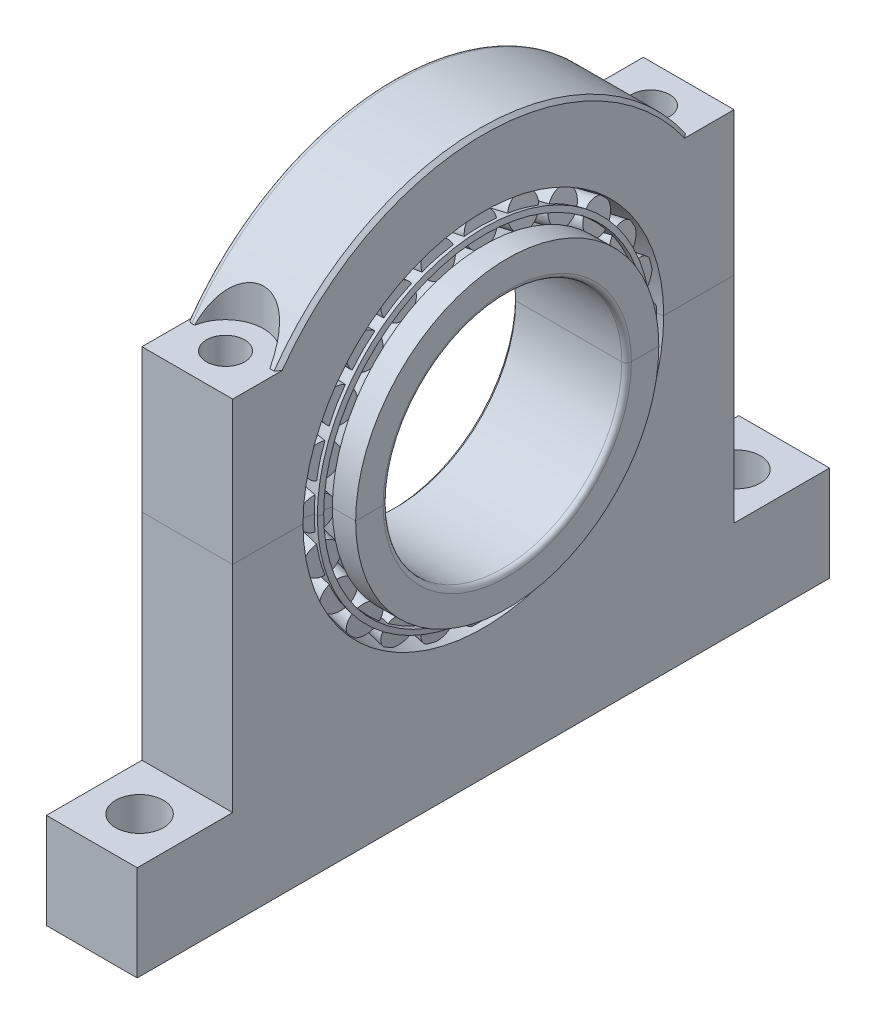
SolidWorks part; units mm, degrees
revolve "OuterRace" add sketch "OutRacSke" angle 360 about L5
sketch "OutRacSke" plane through (0, 0, 0) normal (0, 0, 1) x (1, 0, 0)
  line L0 (-5, 37.7704) -> (-24, 33.8875)
  line L1 (-24, 33.8875) -> (-24, 51.5)
  line L2 (-23, 52.5) -> (-5.76, 52.5)
  line L3 (-5.76, 52.5) -> (-5, 51.74)
  line L4 (-5, 51.74) -> (-5, 37.7704)
  line L5 (-42.5, 0) -> (42.5, 0) construction
  arc A0 (-24, 51.5) -> (-23, 52.5) centre (-23, 51.5) cw
  dimension "D8" = 45
  dimension "Tangle" = 11.55
ref_plane "Plane1" through (0, 0, 0) normal (0, 0, 1) x (1, 0, 0)
ref_plane "Plane2" through (0, 0, 0) normal (0, 1, 0) x (1, 0, 0)
ref_plane "Plane3" through (0, 0, 0) normal (1, 0, 0) x (0, 0, -1)
sketch "Clipboard" plane through (0, 0, 0) normal (0, 0, 1) x (1, 0, 0)
  line L0 (0, 0) -> (10, 0) construction
  line L1 (0, 0) -> (61.9155, -27.5666)
  line L2 (0, 0) -> (45.6773, 20.3368)
  line L3 (0, 0) -> (73.0836, -32.5389)
  line L4 (0, 0) -> (-17.0896, -0.5968)
  line L5 (0, 0) -> (-6.75, 24)
  dimension "Roller_diameter" = 6.75
  dimension "cyl_len" = 17.1
sketch "RolDetSke" plane through (0, 0, 0) normal (0, 0, 1) x (1, 0, 0)
  line L0 (-22.3242, 30.9557) -> (-23, 34.2623)
  line L1 (-22.3242, 30.9557) -> (-5.5705, 34.3795)
  line L2 (-6.2463, 37.6861) -> (-5.5705, 34.3795)
  line L4 (-44.7614, 26.3704) -> (4.5907, 36.456) construction
  line L5 (-6.2463, 37.6861) -> (-23, 34.2623)
  line L9 (-5, 37.7704) -> (-24, 33.8875) construction
  dimension "Roller_diameter" = 6.75
  dimension "dy" = 34.2623
  dimension "D2" = 23
  dimension "cyl_len" = 17.1
revolve "RollerDetailed" add sketch "RolDetSke" angle 360 about L4
sketch "RolSimSke" plane through (0, 0, 0) normal (0, 0, 1) x (1, 0, 0)
  line L0 (0, 0) -> (-32, 0) construction
  line L1 (-23, 34.2623) -> (-6.2463, 37.6861)
  line L2 (-23, 34.2623) -> (-21.6485, 27.649)
  line L3 (-21.6485, 27.649) -> (-4.8948, 31.0728)
  line L4 (-6.2463, 37.6861) -> (-4.8948, 31.0728)
  dimension "Roller_diameter" = 6.75
  dimension "dy" = 34.2623
  dimension "dx" = 23
  dimension "Tangle" = 11.55
revolve "RollersSimplified" [suppressed] add sketch "RolSimSke" angle 360 about L0
ref_axis "Axis1" through (-50, 0, 0) along (1, 0, 0)
pattern_circular "RollersDetailed" count 24 every 15 about axis through (-50, 0, 0) along (1, 0, 0) of "RollerDetailed", "OuterRace"
sketch "InsRacSke" plane through (0, 0, 0) normal (0, 0, 1) x (1, 0, 0)
  line L0 (-21.7107, 27.9865) -> (-24, 27.9865)
  line L1 (-24, 51.5) -> (-24, -51.5) construction
  line L2 (-24, 27.9865) -> (-24, 25.76)
  line L3 (-24, 25.76) -> (-23.24, 25)
  line L4 (-23.24, 25) -> (-1, 25)
  line L5 (0, 26) -> (0, 31.7478)
  line L6 (0, 31.7478) -> (-4.888, 31.7478)
  line L7 (-4.888, 31.7478) -> (-4.888, 31.0728)
  line L8 (-4.888, 31.0728) -> (-21.6417, 27.649)
  line L9 (-21.6417, 27.649) -> (-21.7107, 27.9865)
  line L10 (-42.5, 0) -> (42.5, 0) construction
  arc A0 (-1, 25) -> (0, 26) centre (-1, 26) ccw
  dimension "Tangle" = 11.55
  dimension "cyl_len" = 17.1
  dimension "dy" = 27.649
  dimension "dx" = 21.6417
  dimension "D11" = 45
  dimension "D2" = 24
revolve "InnerRace" add sketch "InsRacSke" angle 360 about L10
sketch "CagSpiSke" plane through (0, 0, 0) normal (0, 0, 1) x (1, 0, 0)
  line L3 (-4.7328, 34.3802) -> (-22.3242, 30.7852)
  line L4 (-22.675, 30.2542) -> (-22.4948, 29.3724)
  line L6 (-42.5, 0) -> (42.5, 0) construction
  arc A1 (-22.3242, 30.7852) -> (-22.675, 30.2542) centre (-22.2341, 30.3443) ccw
  dimension "Tangle" = 11.55
  dimension "radius" = 0.45
  dimension "dx" = 22.3242
  dimension "dy" = 30.7852
  dimension "offset" = 1.35
revolve "CageSpine" add sketch "CagSpiSke" angle 360 about L6
sketch "Esquisse1" plane through (-24, 0, 0) normal (-1, 0, 0) x (0, 0, 1)
  line L0 (0, 0) -> (-68.2811, 0) construction
  line L1 (0, 0) -> (67.9563, 0) construction
  line L2 (-52.5, 0) -> (-52.5, -66.8553) construction
  line L3 (52.5, 0) -> (52.5, -79.7659) construction
  line L4 (-52.5, 0) -> (-52.5, 49.3944) construction
  line L5 (52.5, 0) -> (52.5, 36.4838) construction
  line L6 (-52.5, 30) -> (-41.8599, 30)
  line L7 (52.5, 30) -> (41.8599, 30)
  line L8 (52.5, 30) -> (52.5, -45)
  line L9 (52.5, -45) -> (72.5, -45)
  line L10 (72.5, -45) -> (72.5, -65)
  line L11 (-52.5, 30) -> (-52.5, -45)
  line L12 (-52.5, -45) -> (-72.5, -45)
  line L13 (-72.5, -45) -> (-72.5, -65)
  line L14 (-72.5, -65) -> (72.5, -65)
  circle A0 centre (0, 0) radius 52.5 construction
  circle A1 centre (0, 0) radius 51.5 construction
  arc A2 (-41.8599, 30) -> (41.8599, 30) centre (0, 0) ccw
  dimension "D1" = 30
  dimension "D2" = 20
  dimension "D3" = 20
  dimension "D4" = 65
extrude "Boss.-Extru.1" add sketch "Esquisse1" against normal blind 19
sketch "Esquisse2" plane through (0, 30, 0) normal (0, 1, 0) x (1, 0, 0)
  line L0 (-24, 44.5) -> (-5, 44.5) construction
  line L1 (-24, 41.8599) -> (-24, 52.5) construction
  line L2 (-5, 42.1548) -> (-5, 52.5) construction
  line L3 (-5, 52.5) -> (-24, 52.5) construction
  circle A0 centre (-14.5, 44.5) radius 8
  dimension "D1" = 16
  dimension "D2" = 8
extrude "Enlèv. mat.-Extru.1" cut sketch "Esquisse2" along normal blind 19
sketch "Esquisse3" plane through (0, 30, 0) normal (0, 1, 0) x (1, 0, 0)
  line L0 (-24, 44.5) -> (-5, 44.5) construction
  line L1 (-24, 41.8599) -> (-24, 52.5) construction
  line L2 (-5, 42.1548) -> (-5, 52.5) construction
  line L3 (-5, 52.5) -> (-24, 52.5) construction
  circle A0 centre (-14.5, 44.5) radius 4
  dimension "D2" = 8
  dimension "D1" = 8
extrude "Enlèv. mat.-Extru.2" cut sketch "Esquisse3" against normal blind 60
sketch "Esquisse4" plane through (0, -45, 0) normal (0, 1, 0) x (1, 0, 0)
  line L0 (-24, 62.5) -> (-5, 62.5) construction
  line L1 (-24, 52.5) -> (-24, 72.5) construction
  line L2 (-5, 52.5) -> (-5, 72.5) construction
  circle A0 centre (-14.5, 62.5) radius 5
  dimension "D1" = 10
extrude "Enlèv. mat.-Extru.3" cut sketch "Esquisse4" against normal through all
mirror "Symétrie1" about plane through (0, 0, 0) normal (0, 0, 1) of "Enlèv. mat.-Extru.3", "Enlèv. mat.-Extru.1", "Enlèv. mat.-Extru.2"
sketch "Esquisse5" plane through (-24, 0, 0) normal (-1, 0, 0) x (0, 0, 1)
  line L0 (-52.5, 0) -> (52.5, 0)
  line L1 (-52.5, 30) -> (-52.5, -45) construction
  line L2 (52.5, -45) -> (52.5, 30) construction
split "Fractionner1" trim tools "Esquisse5" bodies to split 109 resulting bodies 111 112
equation "\"cup_SID@OutRacSke\" = \"Race_ID@Clipboard\""
equation "\"chamfer@OutRacSke\" = \"cup_width@OutRacSke\" / 25"
equation "\"D2@RolDetSke\" = \"offset@OutRacSke\" - \"cup_radius@OutRacSke\""
equation "\"dy@RolDetSke\" =  ( ( \"Race_ID@Clipboard\" / 2 ) + ( \"cup_radius@OutRacSke\" ) * tan(\"Tangle@OutRacSke\" * 3.141592654/180) ) * 1.005"
equation "\"cyl_len@RolDetSke\" = \"cyl_len@Clipboard\""
equation "\"Roller_diameter@RolDetSke\" = \"Roller_diameter@Clipboard\""
equation "\"dx@RolSimSke\" = \"offset@OutRacSke\" - \"cup_radius@OutRacSke\""
equation "\"dy@RolSimSke\" =  ( ( \"Race_ID@Clipboard\" / 2 ) + ( \"cup_radius@OutRacSke\" ) * tan(\"Tangle@OutRacSke\" * 3.141592654/180) ) * 1.005"
equation "\"Cyl_Len@RolSimSke\" = \"cyl_len@Clipboard\""
equation "\"Roller_diameter@RolSimSke\" = \"Roller_diameter@Clipboard\""
equation "\"Bore@InsRacSke\" = \"Bore@Clipboard\""
equation "\"Tangle@InsRacSke\" = \"Tangle@OutRacSke\""
equation "\"cyl_len@InsRacSke\" = \"cyl_len@Clipboard\""
equation "\"chamfer@InsRacSke\" = \"chamfer@OutRacSke\""
equation "\"D2@InsRacSke\" = \"OA_width@Clipboard\""
equation "\"dx@InsRacSke\" = \"offset@OutRacSke\" - \"cup_radius@OutRacSke\" -  (  \"Roller_diameter@Clipboard\" * 1.005 )  * sin(\"Tangle@InsRacSke\" * 3.141592654/180)"
equation "\"dy@InsRacSke\" = ( ( \"Race_ID@Clipboard\" / 2 ) + ( \"cup_radius@OutRacSke\" ) * tan(\"Tangle@OutRacSke\" * 3.141592654/180) ) * 1.005 -  ( \"Roller_diameter@Clipboard\" )  * cos(\"Tangle@InsRacSke\" * 3.141592654/180) "
equation "\"front_groove@InsRacSke\" = \"Groove_dp@InsRacSke\" / 2"
equation "\"Tangle@CagSpiSke\" = \"Tangle@OutRacSke\""
equation "\"dx@CagSpiSke\" = ( \"offset@OutRacSke\" - \"cup_radius@OutRacSke\" ) -  (  \"Roller_diameter@Clipboard\" / 2  )  * sin(\"Tangle@InsRacSke\" * 3.141592654/180)"
equation "\"dy@CagSpiSke\" = ( ( \"Race_ID@Clipboard\" / 2 ) + ( \"cup_radius@OutRacSke\" ) * tan(\"Tangle@OutRacSke\" * 3.141592654/180) )  -  ( \"Roller_diameter@Clipboard\" / 2 )  * cos(\"Tangle@InsRacSke\" * 3.141592654/180) "
equation "\"length@CagSpiSke\" = \"cyl_len@Clipboard\" * 1.05"
equation "\"offset@CagSpiSke\" = \"Roller_diameter@Clipboard\" / 5"
equation "\"radius@CagSpiSke\" = \"offset@CagSpiSke\" / 3"
equation "\"D3@CageSpine\" = \"Roller_diameter@Clipboard\" / 6"
equation "\"Max_count@Clipboard\" = int( 3.14159265 / atn(( \"Roller_diameter@Clipboard\" / 2) / sqr( \"dy@CagSpiSke\"  *  \"dy@CagSpiSke\" - ( \"Roller_diameter@Clipboard\" / 2) *  ( \"Roller_diameter@Clipboard\" / 2))))"
equation "\"Max_count@Clipboard\" = ((sgn( \"Max_count@Clipboard\" - \"Count@Clipboard\" )-1)*( \"Max_count@Clipboard\" - \"Count@Clipboard\" ))/-2+ \"Count@Clipboard\""
equation "\"Count@RollersDetailed\" = int( \"Show_count@Clipboard\" ) "
equation "\"Count@RollersDetailed\" = ((sgn( \"Count@RollersDetailed\" - \"Max_count@Clipboard\" )-1)*( \"Count@RollersDetailed\" - \"Max_count@Clipboard\" ))/-2+ \"Max_count@Clipboard\""
equation "\"Count@RollersDetailed\" = ((sgn( \"Count@RollersDetailed\" - \"Min_count@Clipboard\" )+1)*( \"Count@RollersDetailed\" - \"Min_count@Clipboard\"))/2 +\"Min_count@Clipboard\""
equation "\"Angle@RollersDetailed\" = 360.0 / \"Max_count@Clipboard\""
equation "\"Angle@CageSpine\" =  \"Angle@RollersDetailed\" * ( \"Count@RollersDetailed\" -1 + int( \"Count@RollersDetailed\" / \"Max_count@Clipboard\" ) )  + 0.001 -  int( \"Count@RollersDetailed\" / \"Max_count@Clipboard\" ) * 0.001"
equation "\"Angle@CageSpine\" =  \"Angle@CageSpine\" * int( \"Min_count@Clipboard\" / 2) + int(1 / \"Min_count@Clipboard\")  * 0.001"
equation "\"Tangle@RolSimSke\" = \"Tangle@OutRacSke\""
